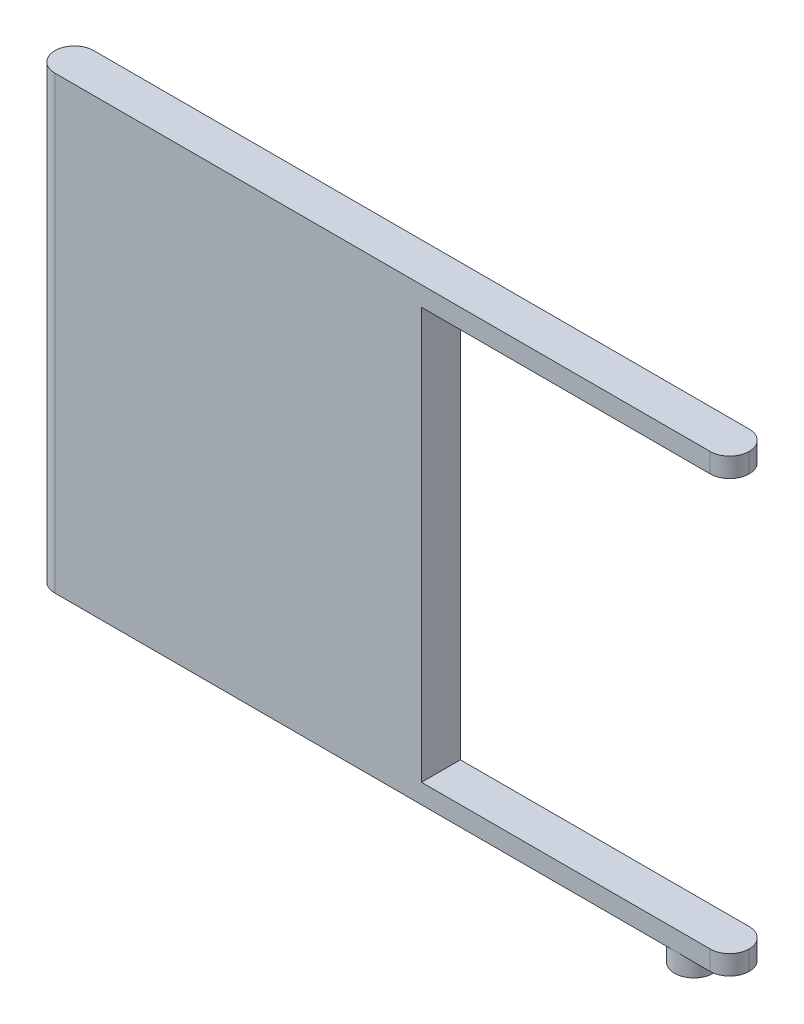
SolidWorks part; units mm, degrees
ref_plane "Front Plane" through (0, 0, 0) normal (0, 0, 1) x (1, 0, 0)
ref_plane "Top Plane" through (0, 0, 0) normal (0, 1, 0) x (1, 0, 0)
ref_plane "Right Plane" through (0, 0, 0) normal (1, 0, 0) x (0, 0, -1)
sketch "Sketch1" plane through (0, 0, 0) normal (0, 1, 0) x (1, 0, 0)
  line L0 (-19.5, 1.5) -> (-19.5, -1.5)
  line L1 (-49.25, 1.5) -> (4.25, 1.5)
  line L2 (-49.25, 1.5) -> (-49.25, -1.5)
  line L3 (-49.25, -1.5) -> (4.25, -1.5)
  line L4 (4.25, 1.5) -> (4.25, -1.5)
  point P4 (4.25, 0)
  dimension "D1" = 53.5
  dimension "D2" = 4.25
  dimension "D3" = 3
  dimension "D4" = 29.75
extrude "Boss-Extrude1" add sketch "Sketch1" along normal blind 1.5 contours L4 L1 L0 L3 | L2 L3 L0 L1 region at (-7.625, 0, 0) region at (-34.375, 0, 0)
ref_plane "Plane1" through (0, 34.7, 0) normal (0, 1, 0) x (1, 0, 0)
extrude "Boss-Extrude2" add sketch "Sketch1<3>" along normal up to surface (34.7 mm away) contours L2 L3 L0 L1 region at (-34.375, 0, 0) up to plane "Plane1"
sketch "Sketch1<3>" plane through (0, 0, 0) normal (0, 1, 0) x (1, 0, 0) same geometry as "Sketch1"
extrude "Boss-Extrude3" add sketch "Sketch1<4>" against normal blind 1.5 from surface contours L4 L1 L0 L3 region at (-7.625, 0, 0) starting at plane "Plane1"
sketch "Sketch1<4>" plane through (0, 0, 0) normal (0, 1, 0) x (1, 0, 0) same geometry as "Sketch1"
sketch "Sketch3" plane through (0, 0, 0) normal (0, -1, 0) x (1, 0, 0)
  circle A0 centre (0, 0) radius 1.5
  dimension "D1" = 3
extrude "Boss-Extrude4" add sketch "Sketch3" along normal blind 1.5
fillet "Fillet1" radius 1.5 6 edges at (4.25, 33.95, 1.5) (4.25, 33.95, -1.5) (4.25, 0.75, 1.5) (4.25, 0.75, -1.5) (-49.25, 17.35, -1.5) (-49.25, 17.35, 1.5)
